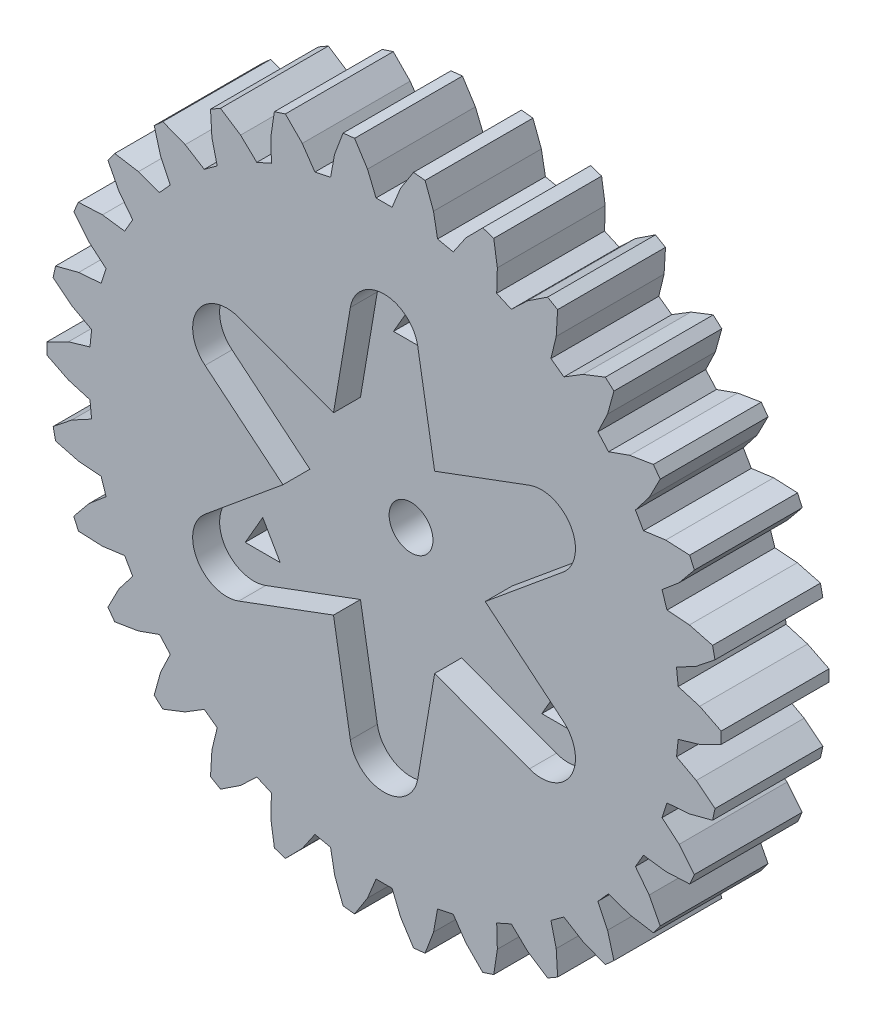
SolidWorks part; units mm, degrees
material "ABS"
ref_plane "Front Plane" through (0, 0, 0) normal (0, 0, 1) x (1, 0, 0)
ref_plane "Top Plane" through (0, 0, 0) normal (0, 1, 0) x (1, 0, 0)
ref_plane "Right Plane" through (0, 0, 0) normal (1, 0, 0) x (0, 0, -1)
sketch "Sketch1" plane through (0, 0, 0) normal (0, 0, 1) x (1, 0, 0)
  line L0 (67.8387, 65.5179) -> (69.435, 65.0497)
  line L1 (69.435, 65.0497) -> (71.0262, 64.252)
  line L2 (71.0262, 64.252) -> (71.0262, 63.394)
  line L3 (71.0262, 63.394) -> (69.435, 62.5962)
  line L4 (69.435, 62.5962) -> (67.8387, 62.1281)
  line L5 (67.8387, 62.1281) -> (67.7144, 60.9457)
  line L6 (67.7144, 60.9457) -> (69.1786, 60.156)
  line L7 (69.1786, 60.156) -> (70.5691, 59.0447)
  line L8 (70.5691, 59.0447) -> (70.3908, 58.2056)
  line L9 (70.3908, 58.2056) -> (68.6684, 57.756)
  line L10 (68.6684, 57.756) -> (67.0096, 57.6301)
  line L11 (67.0096, 57.6301) -> (66.6423, 56.4993)
  line L12 (66.6423, 56.4993) -> (67.9102, 55.4225)
  line L13 (67.9102, 55.4225) -> (69.0393, 54.0464)
  line L14 (69.0393, 54.0464) -> (68.6904, 53.2627)
  line L15 (68.6904, 53.2627) -> (66.9123, 53.181)
  line L16 (66.9123, 53.181) -> (65.2636, 53.4028)
  line L17 (65.2636, 53.4028) -> (64.669, 52.3732)
  line L18 (64.669, 52.3732) -> (65.6854, 51.0562)
  line L19 (65.6854, 51.0562) -> (66.5038, 49.4753)
  line L20 (66.5038, 49.4753) -> (65.9995, 48.7814)
  line L21 (65.9995, 48.7814) -> (64.2432, 49.0712)
  line L22 (64.2432, 49.0712) -> (62.6766, 49.6308)
  line L23 (62.6766, 49.6308) -> (61.8811, 48.7473)
  line L24 (61.8811, 48.7473) -> (62.6014, 47.2478)
  line L25 (62.6014, 47.2478) -> (63.0732, 45.5314)
  line L26 (63.0732, 45.5314) -> (62.4357, 44.9574)
  line L27 (62.4357, 44.9574) -> (60.778, 45.606)
  line L28 (60.778, 45.606) -> (59.3621, 46.4791)
  line L29 (59.3621, 46.4791) -> (58.4003, 45.7802)
  line L30 (58.4003, 45.7802) -> (58.793, 44.1638)
  line L31 (58.793, 44.1638) -> (58.8977, 42.3868)
  line L32 (58.8977, 42.3868) -> (58.1548, 41.9579)
  line L33 (58.1548, 41.9579) -> (56.6682, 42.9369)
  line L34 (56.6682, 42.9369) -> (55.4646, 44.0854)
  line L35 (55.4646, 44.0854) -> (54.3785, 43.6018)
  line L36 (54.3785, 43.6018) -> (54.4267, 41.939)
  line L37 (54.4267, 41.939) -> (54.1596, 40.1792)
  line L38 (54.1596, 40.1792) -> (53.3436, 39.914)
  line L39 (53.3436, 39.914) -> (52.0932, 41.1808)
  line L40 (52.0932, 41.1808) -> (51.1547, 42.5544)
  line L41 (51.1547, 42.5544) -> (49.9918, 42.3072)
  line L42 (49.9918, 42.3072) -> (49.6932, 40.6706)
  line L43 (49.6932, 40.6706) -> (49.066, 39.0048)
  line L44 (49.066, 39.0048) -> (48.2128, 38.9151)
  line L45 (48.2128, 38.9151) -> (47.253, 40.4142)
  line L46 (47.253, 40.4142) -> (46.6207, 41.9528)
  line L47 (46.6207, 41.9528) -> (45.4317, 41.9528)
  line L48 (45.4317, 41.9528) -> (44.7994, 40.4142)
  line L49 (44.7994, 40.4142) -> (43.8396, 38.9151)
  line L50 (43.8396, 38.9151) -> (42.9864, 39.0048)
  line L51 (42.9864, 39.0048) -> (42.3592, 40.6706)
  line L52 (42.3592, 40.6706) -> (42.0606, 42.3072)
  line L53 (42.0606, 42.3072) -> (40.8977, 42.5544)
  line L54 (40.8977, 42.5544) -> (39.9592, 41.1808)
  line L55 (39.9592, 41.1808) -> (38.7088, 39.914)
  line L56 (38.7088, 39.914) -> (37.8928, 40.1792)
  line L57 (37.8928, 40.1792) -> (37.6257, 41.939)
  line L58 (37.6257, 41.939) -> (37.6739, 43.6018)
  line L59 (37.6739, 43.6018) -> (36.5878, 44.0854)
  line L60 (36.5878, 44.0854) -> (35.3842, 42.9369)
  line L61 (35.3842, 42.9369) -> (33.8976, 41.9579)
  line L62 (33.8976, 41.9579) -> (33.1547, 42.3868)
  line L63 (33.1547, 42.3868) -> (33.2594, 44.1638)
  line L64 (33.2594, 44.1638) -> (33.6521, 45.7802)
  line L65 (33.6521, 45.7802) -> (32.6903, 46.4791)
  line L66 (32.6903, 46.4791) -> (31.2744, 45.606)
  line L67 (31.2744, 45.606) -> (29.6167, 44.9574)
  line L68 (29.6167, 44.9574) -> (28.9792, 45.5314)
  line L69 (28.9792, 45.5314) -> (29.451, 47.2478)
  line L70 (29.451, 47.2478) -> (30.1713, 48.7473)
  line L71 (30.1713, 48.7473) -> (29.3758, 49.6308)
  line L72 (29.3758, 49.6308) -> (27.8092, 49.0712)
  line L73 (27.8092, 49.0712) -> (26.0529, 48.7814)
  line L74 (26.0529, 48.7814) -> (25.5486, 49.4753)
  line L75 (25.5486, 49.4753) -> (26.367, 51.0562)
  line L76 (26.367, 51.0562) -> (27.3834, 52.3732)
  line L77 (27.3834, 52.3732) -> (26.7888, 53.4028)
  line L78 (26.7888, 53.4028) -> (25.1401, 53.181)
  line L79 (25.1401, 53.181) -> (23.362, 53.2627)
  line L80 (23.362, 53.2627) -> (23.0131, 54.0464)
  line L81 (23.0131, 54.0464) -> (24.1422, 55.4225)
  line L82 (24.1422, 55.4225) -> (25.4101, 56.4993)
  line L83 (25.4101, 56.4993) -> (25.0428, 57.6301)
  line L84 (25.0428, 57.6301) -> (23.384, 57.756)
  line L85 (23.384, 57.756) -> (21.6616, 58.2056)
  line L86 (21.6616, 58.2056) -> (21.4833, 59.0447)
  line L87 (21.4833, 59.0447) -> (22.8738, 60.156)
  line L88 (22.8738, 60.156) -> (24.338, 60.9457)
  line L89 (24.338, 60.9457) -> (24.2137, 62.1281)
  line L90 (24.2137, 62.1281) -> (22.6174, 62.5962)
  line L91 (22.6174, 62.5962) -> (21.0262, 63.394)
  line L92 (21.0262, 63.394) -> (21.0262, 64.252)
  line L93 (21.0262, 64.252) -> (22.6174, 65.0497)
  line L94 (22.6174, 65.0497) -> (24.2137, 65.5179)
  line L95 (24.2137, 65.5179) -> (24.338, 66.7003)
  line L96 (24.338, 66.7003) -> (22.8738, 67.49)
  line L97 (22.8738, 67.49) -> (21.4833, 68.6013)
  line L98 (21.4833, 68.6013) -> (21.6616, 69.4404)
  line L99 (21.6616, 69.4404) -> (23.384, 69.89)
  line L100 (23.384, 69.89) -> (25.0428, 70.0159)
  line L101 (25.0428, 70.0159) -> (25.4101, 71.1467)
  line L102 (25.4101, 71.1467) -> (24.1422, 72.2235)
  line L103 (24.1422, 72.2235) -> (23.0131, 73.5996)
  line L104 (23.0131, 73.5996) -> (23.362, 74.3832)
  line L105 (23.362, 74.3832) -> (25.1401, 74.465)
  line L106 (25.1401, 74.465) -> (26.7888, 74.2432)
  line L107 (26.7888, 74.2432) -> (27.3834, 75.2728)
  line L108 (27.3834, 75.2728) -> (26.367, 76.5898)
  line L109 (26.367, 76.5898) -> (25.5486, 78.1707)
  line L110 (25.5486, 78.1707) -> (26.0529, 78.8646)
  line L111 (26.0529, 78.8646) -> (27.8092, 78.5748)
  line L112 (27.8092, 78.5748) -> (29.3758, 78.0151)
  line L113 (29.3758, 78.0151) -> (30.1713, 78.8987)
  line L114 (30.1713, 78.8987) -> (29.451, 80.3982)
  line L115 (29.451, 80.3982) -> (28.9792, 82.1145)
  line L116 (28.9792, 82.1145) -> (29.6167, 82.6886)
  line L117 (29.6167, 82.6886) -> (31.2744, 82.04)
  line L118 (31.2744, 82.04) -> (32.6903, 81.1669)
  line L119 (32.6903, 81.1669) -> (33.6521, 81.8658)
  line L120 (33.6521, 81.8658) -> (33.2594, 83.4822)
  line L121 (33.2594, 83.4822) -> (33.1547, 85.2592)
  line L122 (33.1547, 85.2592) -> (33.8976, 85.6881)
  line L123 (33.8976, 85.6881) -> (35.3842, 84.7091)
  line L124 (35.3842, 84.7091) -> (36.5878, 83.5606)
  line L125 (36.5878, 83.5606) -> (37.6739, 84.0442)
  line L126 (37.6739, 84.0442) -> (37.6257, 85.707)
  line L127 (37.6257, 85.707) -> (37.8928, 87.4668)
  line L128 (37.8928, 87.4668) -> (38.7088, 87.732)
  line L129 (38.7088, 87.732) -> (39.9592, 86.4652)
  line L130 (39.9592, 86.4652) -> (40.8977, 85.0916)
  line L131 (40.8977, 85.0916) -> (42.0606, 85.3388)
  line L132 (42.0606, 85.3388) -> (42.3592, 86.9754)
  line L133 (42.3592, 86.9754) -> (42.9864, 88.6412)
  line L134 (42.9864, 88.6412) -> (43.8396, 88.7309)
  line L135 (43.8396, 88.7309) -> (44.7994, 87.2318)
  line L136 (44.7994, 87.2318) -> (45.4317, 85.6932)
  line L137 (45.4317, 85.6932) -> (46.6207, 85.6932)
  line L138 (46.6207, 85.6932) -> (47.253, 87.2318)
  line L139 (47.253, 87.2318) -> (48.2128, 88.7309)
  line L140 (48.2128, 88.7309) -> (49.066, 88.6412)
  line L141 (49.066, 88.6412) -> (49.6932, 86.9754)
  line L142 (49.6932, 86.9754) -> (49.9918, 85.3388)
  line L143 (49.9918, 85.3388) -> (51.1547, 85.0916)
  line L144 (51.1547, 85.0916) -> (52.0932, 86.4652)
  line L145 (52.0932, 86.4652) -> (53.3436, 87.732)
  line L146 (53.3436, 87.732) -> (54.1596, 87.4668)
  line L147 (54.1596, 87.4668) -> (54.4267, 85.707)
  line L148 (54.4267, 85.707) -> (54.3785, 84.0442)
  line L149 (54.3785, 84.0442) -> (55.4646, 83.5606)
  line L150 (55.4646, 83.5606) -> (56.6682, 84.7091)
  line L151 (56.6682, 84.7091) -> (58.1548, 85.6881)
  line L152 (58.1548, 85.6881) -> (58.8977, 85.2592)
  line L153 (58.8977, 85.2592) -> (58.793, 83.4822)
  line L154 (58.793, 83.4822) -> (58.4003, 81.8658)
  line L155 (58.4003, 81.8658) -> (59.3621, 81.1669)
  line L156 (59.3621, 81.1669) -> (60.778, 82.04)
  line L157 (60.778, 82.04) -> (62.4357, 82.6886)
  line L158 (62.4357, 82.6886) -> (63.0732, 82.1145)
  line L159 (63.0732, 82.1145) -> (62.6014, 80.3982)
  line L160 (62.6014, 80.3982) -> (61.8811, 78.8987)
  line L161 (61.8811, 78.8987) -> (62.6766, 78.0151)
  line L162 (62.6766, 78.0151) -> (64.2432, 78.5748)
  line L163 (64.2432, 78.5748) -> (65.9995, 78.8646)
  line L164 (65.9995, 78.8646) -> (66.5038, 78.1707)
  line L165 (66.5038, 78.1707) -> (65.6854, 76.5898)
  line L166 (65.6854, 76.5898) -> (64.669, 75.2728)
  line L167 (64.669, 75.2728) -> (65.2636, 74.2432)
  line L168 (65.2636, 74.2432) -> (66.9123, 74.465)
  line L169 (66.9123, 74.465) -> (68.6904, 74.3832)
  line L170 (68.6904, 74.3832) -> (69.0393, 73.5996)
  line L171 (69.0393, 73.5996) -> (67.9102, 72.2235)
  line L172 (67.9102, 72.2235) -> (66.6423, 71.1467)
  line L173 (66.6423, 71.1467) -> (67.0096, 70.0159)
  line L174 (67.0096, 70.0159) -> (68.6684, 69.89)
  line L175 (68.6684, 69.89) -> (70.3908, 69.4404)
  line L176 (70.3908, 69.4404) -> (70.5691, 68.6013)
  line L177 (70.5691, 68.6013) -> (69.1786, 67.49)
  line L178 (69.1786, 67.49) -> (67.7144, 66.7003)
  line L179 (67.7144, 66.7003) -> (67.8387, 65.5179)
  line L180 (48.6394, 38.96) -> (43.413, 88.686) construction
  line L181 (21.0262, 63.823) -> (71.0262, 63.823) construction
  point P184 (46.0262, 63.823)
sketch "Sketch3" plane through (0, 0, 0) normal (0, 0, 1) x (1, 0, 0)
  circle A0 centre (46.0262, 63.823) radius 18
  dimension "D1" = 36
sketch "Sketch4" plane through (0, 0, 0) normal (0, 0, 1) x (1, 0, 0)
  line L0 (42.2762, 70.3182) -> (46.0262, 63.823) construction
  line L1 (48.6394, 38.96) -> (43.413, 88.686) construction
  line L2 (46.0262, 63.823) -> (46.0262, 79.823) construction
  line L3 (42.2762, 70.3182) -> (43.5262, 77.7103)
  line L4 (49.7762, 70.3182) -> (48.5262, 77.7103)
  line L5 (46.0262, 63.823) -> (49.7762, 70.3182) construction
  line L6 (49.7762, 70.3182) -> (56.8029, 72.9317)
  line L7 (53.5262, 63.823) -> (59.3029, 68.6016)
  line L8 (53.5262, 63.823) -> (59.3029, 59.0444)
  line L9 (49.7762, 57.3278) -> (56.8029, 54.7143)
  line L10 (49.7762, 57.3278) -> (48.5262, 49.9357)
  line L11 (42.2762, 57.3278) -> (43.5262, 49.9357)
  line L12 (42.2762, 57.3278) -> (35.2495, 54.7143)
  line L13 (38.5262, 63.823) -> (32.7495, 59.0444)
  line L14 (38.5262, 63.823) -> (32.7495, 68.6016)
  line L15 (42.2762, 70.3182) -> (35.2495, 72.9317)
  arc A0 (48.5262, 77.7103) -> (43.5262, 77.7103) centre (46.0262, 77.2875) ccw
  circle A1 centre (46.0262, 63.823) radius 7.5 construction
  arc A2 (59.3029, 68.6016) -> (56.8029, 72.9317) centre (57.6868, 70.5553) ccw
  circle A3 centre (46.0262, 63.823) radius 7.5 construction
  arc A4 (56.8029, 54.7143) -> (59.3029, 59.0444) centre (57.6868, 57.0907) ccw
  circle A5 centre (46.0262, 63.823) radius 7.5 construction
  arc A6 (43.5262, 49.9357) -> (48.5262, 49.9357) centre (46.0262, 50.3585) ccw
  circle A7 centre (46.0262, 63.823) radius 7.5 construction
  arc A8 (32.7495, 59.0444) -> (35.2495, 54.7143) centre (34.3656, 57.0907) ccw
  circle A9 centre (46.0262, 63.823) radius 7.5 construction
  arc A10 (35.2495, 72.9317) -> (32.7495, 68.6016) centre (34.3656, 70.5553) ccw
  circle A11 centre (46.0262, 63.823) radius 7.5 construction
  point P0 (46.0262, 63.823)
  point P43 (46.0262, 63.823)
  dimension "D1" = 16
  dimension "D2" = 6
  dimension "D3" = 7.5
  dimension "D4" = 5
extrude "Boss-Extrude1" add sketch "Sketch1" against normal blind 8
sketch "Sketch5" plane through (0, 0, 0) normal (0, 0, 1) x (1, 0, 0)
  circle A0 centre (46.0262, 63.823) radius 1.625
  point P0 (46.0262, 63.823)
  dimension "D1" = 3.25
sketch "Sketch7" plane through (0, 0, -8) normal (0, 0, -1) x (-1, 0, 0)
  circle A0 centre (-46.0262, 63.823) radius 2.875
  point P0 (-46.0262, 63.823)
  dimension "D1" = 5.75
extrude "Cut-Extrude4" cut sketch "Sketch4" against normal blind 2
extrude "Cut-Extrude5" cut sketch "Sketch5" against normal through all
extrude "Cut-Extrude6" cut sketch "Sketch7" against normal blind 1.5
sketch "Sketch9" plane through (0, 0, 0) normal (0, 0, 1) x (1, 0, 0)
  line L0 (46.0262, 63.823) -> (46.0262, 81.823) construction
  line L1 (57.0247, 58.973) -> (55.7257, 56.723)
  line L2 (47.3252, 75.773) -> (46.0262, 78.023)
  line L3 (46.0262, 78.023) -> (44.7272, 75.773)
  line L4 (44.7272, 75.773) -> (47.3252, 75.773)
  line L5 (55.7257, 56.723) -> (58.3238, 56.723)
  line L6 (58.3238, 56.723) -> (57.0247, 58.973)
  line L7 (46.0262, 63.823) -> (61.6147, 54.823) construction
  line L8 (36.3267, 56.723) -> (35.0277, 58.973)
  line L9 (35.0277, 58.973) -> (33.7286, 56.723)
  line L10 (33.7286, 56.723) -> (36.3267, 56.723)
  line L11 (46.0262, 63.823) -> (30.4377, 54.823) construction
  circle A0 centre (46.0262, 63.823) radius 18 construction
  circle A1 centre (46.0262, 76.523) radius 0.75 construction
  point P0 (46.0262, 63.823)
  point P22 (46.0262, 63.823)
  dimension "D1" = 1.5
  dimension "D2" = 12.7
  dimension "D3" = 3
extrude "Cut-Extrude7" cut sketch "Sketch9" against normal through all
